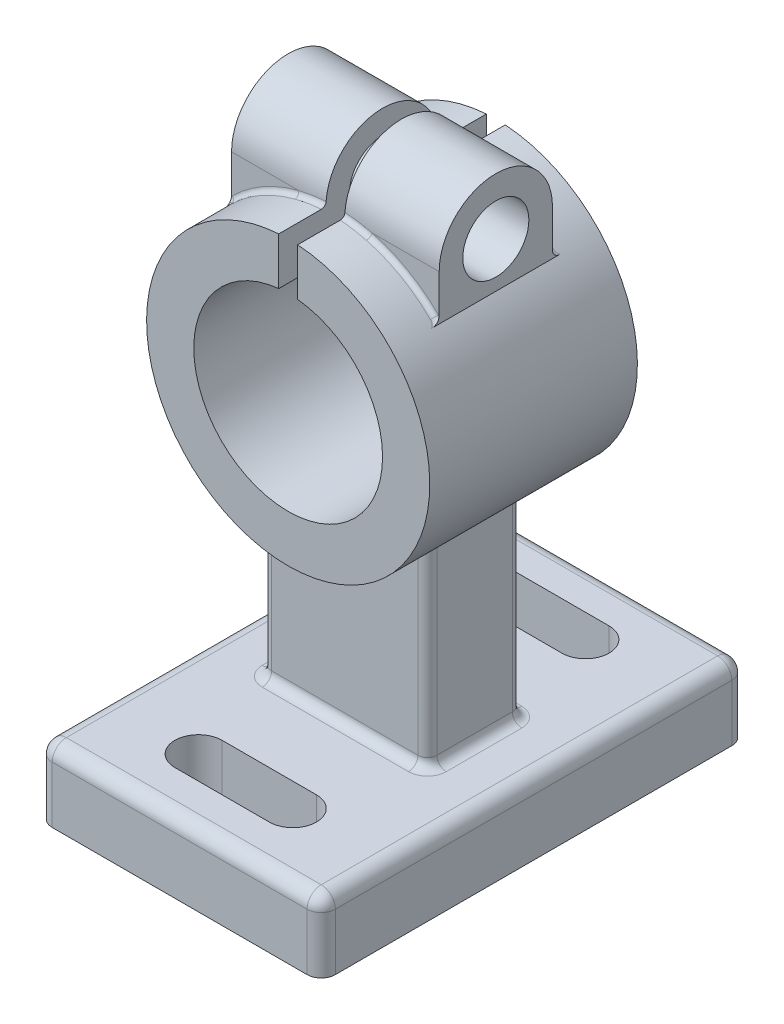
SolidWorks part; units mm, degrees
ref_plane "前基準面" through (0, 0, 0) normal (0, 0, 1) x (1, 0, 0)
ref_plane "上基準面" through (0, 0, 0) normal (0, 1, 0) x (1, 0, 0)
ref_plane "右基準面" through (0, 0, 0) normal (1, 0, 0) x (0, 0, -1)
sketch "草圖3" plane through (0, 0, 0) normal (0, 0, 1) x (1, 0, 0)
  line L0 (0, 0) -> (0, 65) construction
  circle A0 centre (0, 65) radius 30
  circle A1 centre (0, 65) radius 20
  dimension "D2" = 60
  dimension "D3" = 40
  dimension "D1" = 65
extrude "填料-伸長2" add sketch "草圖3" along normal mid plane 44
sketch "草圖4" plane through (0, 0, 0) normal (0, 0, 1) x (1, 0, 0)
  line L0 (-17.5, 0) -> (17.5, 0)
  line L1 (17.5, 0) -> (17.5, 40.633)
  line L2 (-17.5, 0) -> (-17.5, 40.633)
  circle A0 centre (0, 65) radius 30 construction
  circle A2 centre (0, 65) radius 30
  arc A3 (-17.5, 40.633) -> (17.5, 40.633) centre (0, 65) ccw
  dimension "D1" = 35
  dimension "D2" = 0
extrude "填料-伸長3" add sketch "草圖4" along normal mid plane 20
sketch "草圖7" plane through (0, 0, 0) normal (0, 0, 1) x (1, 0, 0)
  line L0 (-30, 0) -> (30, 0)
  line L1 (30, 0) -> (30, -15)
  line L2 (30, -15) -> (-30, -15)
  line L3 (-30, -15) -> (-30, 0)
  dimension "D1" = 15
  dimension "D2" = 60
extrude "填料-伸長5" add sketch "草圖7" along normal mid plane 90
fillet "圓角3" radius 3 8 edges at (30, -7.5, -45) (0, 0, -45) (-30, -7.5, -45) (30, 0, 0) (30, -7.5, 45) (-30, -7.5, 45) (-30, 0, 0) (0, 0, 45)
fillet "圓角4" radius 2 8 edges at (17.5, 0, 0) (0, 0, 10) (-17.5, 0, 0) (0, 0, -10) (17.5, 20.3165, 10) (17.5, 20.3165, -10) (-17.5, 20.3165, 10) (-17.5, 20.3165, -10)
sketch "草圖8" plane through (0, 0, 0) normal (1, 0, 0) x (0, 0, -1)
  line L0 (22, 95) -> (-22, 95) construction
  line L1 (22, 85) -> (-22, 85) construction
  line L3 (-14, 85) -> (14, 85)
  line L4 (12, 87) -> (12, 95)
  line L5 (-12, 95) -> (-12, 87)
  circle A0 centre (0, 95) radius 7
  arc A3 (14, 85) -> (12, 87) centre (14, 87) cw
  arc A4 (12, 95) -> (-12, 95) centre (0, 95) ccw
  arc A5 (-12, 87) -> (-14, 85) centre (-14, 87) cw
  point P25 (0, 85)
  dimension "D1" = 14
  dimension "D2" = 2
  dimension "D3" = 2
  dimension "D4" = 12
extrude "填料-伸長7" add sketch "草圖8" along normal mid plane 44
sketch "草圖9" plane through (0, 0, 0) normal (0, 0, 1) x (1, 0, 0)
  line L0 (-2, 107) -> (-2, 78.3737)
  line L1 (22, 107) -> (-22, 107) construction
  line L2 (-2, 78.3737) -> (2, 78.3737)
  line L3 (2, 78.3737) -> (2, 107)
  line L4 (2, 107) -> (-2, 107)
  line L5 (0, 0) -> (0, 128.486) construction
  point P9 (0, 107)
  dimension "D1" = 4
extrude "除料-伸長1" cut sketch "草圖9" against normal mid plane 44
fillet "圓角5" radius 1 8 edges at (18.711, 88.4499, -15.3776) (11.8798, 92.5476, -12) (-11.8798, 92.5476, -12) (-21.3348, 86.0909, -12.2185) (21.3348, 86.0909, 12.2185) (11.8798, 92.5476, 12) (-11.8798, 92.5476, 12) (-21.4043, 86.0204, 12.2563)
sketch "草圖10" plane through (22, 0, 0) normal (1, 0, 0) x (0, 0, -1)
  circle A0 centre (0, 95) radius 7
  dimension "D1" = 14
extrude "除料-伸長2" cut sketch "草圖10" against normal through all
sketch "草圖12" plane through (0, 0, 0) normal (0, 1, 0) x (1, 0, 0)
  line L0 (-10, 36) -> (10, 36)
  line L1 (-10, 26) -> (10, 26)
  line L2 (-10, -26) -> (10, -26)
  line L3 (-10, -36) -> (10, -36)
  line L4 (0, 42) -> (0, -42) construction
  line L5 (27, 42) -> (-27, 42) construction
  line L6 (-27, -42) -> (27, -42) construction
  line L7 (-10, 31) -> (10, 31) construction
  line L8 (-10, -31) -> (-10, 31) construction
  line L9 (-10, 0) -> (0, 0) construction
  arc A0 (-10, 36) -> (-10, 26) centre (-10, 31) ccw
  arc A1 (10, 36) -> (10, 26) centre (10, 31) cw
  arc A2 (-10, -26) -> (-10, -36) centre (-10, -31) ccw
  arc A3 (10, -26) -> (10, -36) centre (10, -31) cw
  point P18 (0, 31)
  dimension "D4" = 10
  dimension "D1" = 20
  dimension "D2" = 10
  dimension "D3" = 62
extrude "除料-伸長3" cut sketch "草圖12" against normal through all
